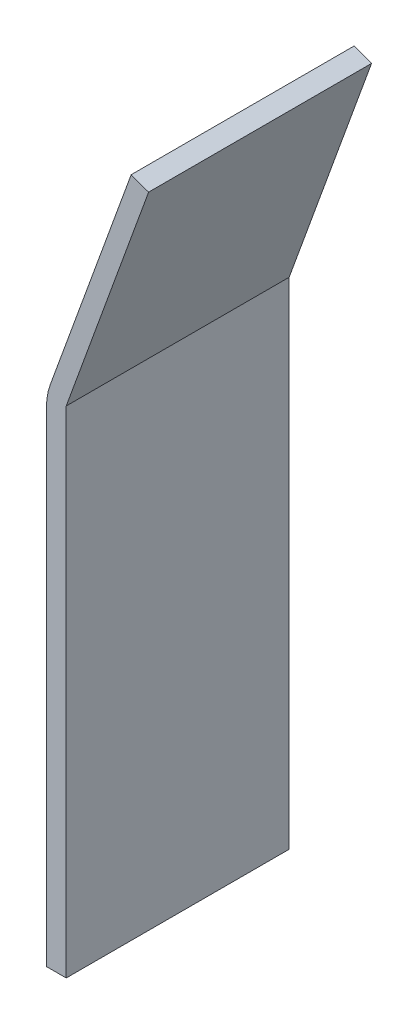
SolidWorks part; units mm, degrees
ref_plane "Plan de face" through (0, 0, 0) normal (0, 0, 1) x (1, 0, 0)
ref_plane "Plan de dessus" through (0, 0, 0) normal (0, 1, 0) x (1, 0, 0)
ref_plane "Plan de droite" through (0, 0, 0) normal (1, 0, 0) x (0, 0, -1)
sketch "Esquisse1" plane through (0, 0, 0) normal (0, 0, 1) x (1, 0, 0)
  line L0 (0, 0) -> (0, 80)
  line L1 (0, 80) -> (13.6808, 117.5877)
  line L2 (13.6808, 117.5877) -> (16.4999, 116.5616)
  line L3 (16.4999, 116.5616) -> (3.1925, 80)
  line L4 (3.1925, 80) -> (3.1925, 0)
  line L5 (3.1925, 0) -> (0, 0)
  line L6 (0, 80) -> (50000, 80) construction
  dimension "D1" = 80
  dimension "D2" = 40
  dimension "D3" = 3
  dimension "D4" = 70
extrude "Boss.-Extru.1" add sketch "Esquisse1" along normal blind 18 and the other way blind 18
fillet "Congé1" radius 10 1 edges at (0, 80, 0)
